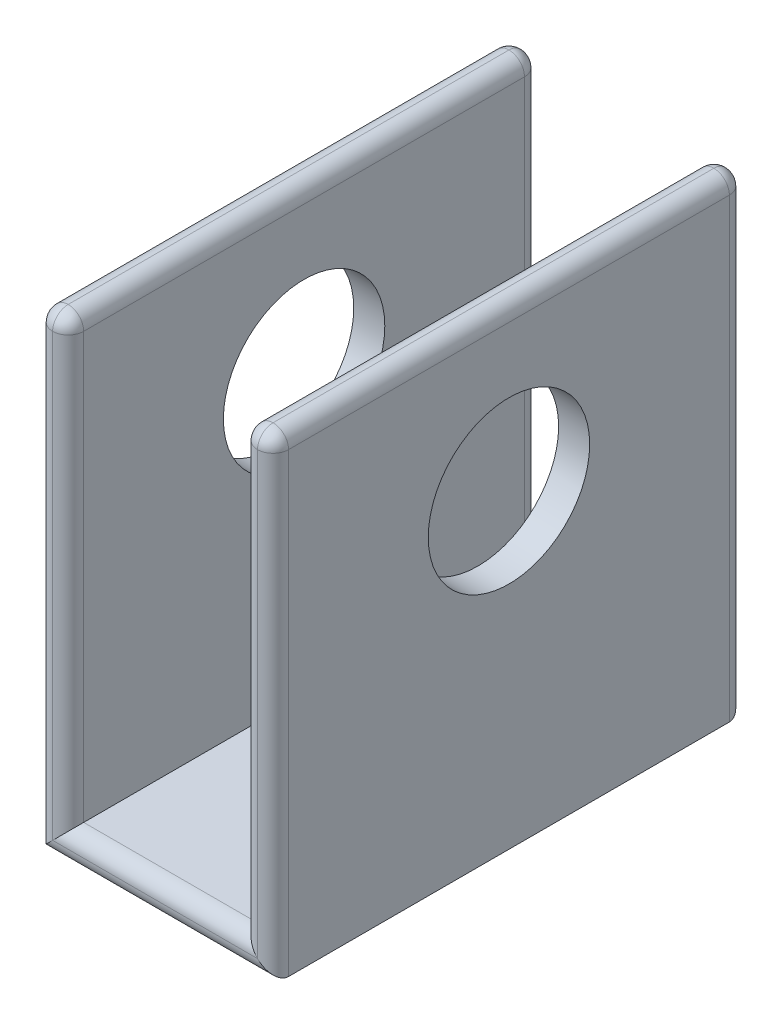
SolidWorks part; units mm, degrees
ref_plane "Front Plane" through (0, 0, 0) normal (0, 0, 1) x (1, 0, 0)
ref_plane "Top Plane" through (0, 0, 0) normal (0, 1, 0) x (1, 0, 0)
ref_plane "Right Plane" through (0, 0, 0) normal (1, 0, 0) x (0, 0, -1)
sketch "Sketch1" plane through (0, 0, 0) normal (0, 0, 1) x (1, 0, 0)
  line L0 (0, 0) -> (0, 23.7806) construction
  line L1 (-9.5, 0) -> (9.5, 0)
  line L2 (9.5, 0) -> (9.5, 38)
  line L3 (-9.5, 0) -> (-9.5, 38)
  line L4 (7, 2.5) -> (7, 36.75)
  line L5 (-7, 2.5) -> (7, 2.5)
  line L6 (-7, 2.5) -> (-7, 36.75)
  line L7 (-9.5, 38) -> (-8.25, 38)
  line L8 (8.25, 38) -> (9.5, 38)
  line L9 (7, 2.5) -> (7, 38) construction
  line L10 (-7, 2.5) -> (-7, 38) construction
  arc A0 (7, 36.75) -> (8.25, 38) centre (8.25, 36.75) cw
  arc A1 (-7, 36.75) -> (-8.25, 38) centre (-8.25, 36.75) ccw
  dimension "D4" = 1.25
  dimension "D1" = 19
  dimension "D2" = 38
  dimension "D3" = 2.5
extrude "Boss-Extrude1" add sketch "Sketch1" along normal blind 38 contours L8 L2 L1 L3 L7 A1 L6 L5 L4 A0
sketch "Sketch2" plane through (9.5, 0, 0) normal (1, 0, 0) x (0, 0, -1)
  line L0 (-19, 38) -> (-19, 0) construction
  line L1 (-38, 38) -> (0, 38) construction
  line L2 (-38, 0) -> (0, 0) construction
  circle A0 centre (-19, 25) radius 6.5
  dimension "D1" = 13
  dimension "D2" = 13
extrude "Cut-Extrude1" cut sketch "Sketch2" against normal through all
fillet "Fillet1" radius 1.25 18 edges at (7.3661, 37.6339, 0) (-7.3661, 37.6339, 0) (9.5, 19, 38) (0, 0, 38) (-9.5, 19, 38) (-7.3661, 37.6339, 38) (-7, 19.625, 38) (0, 2.5, 38) (7, 19.625, 38) (7.3661, 37.6339, 38) (7, 19.625, 0) (9.5, 19, 0) (0, 0, 0) (0, 2.5, 0) (-7, 19.625, 0) (-9.5, 19, 0) (-9.5, 38, 19) (9.5, 38, 19)
